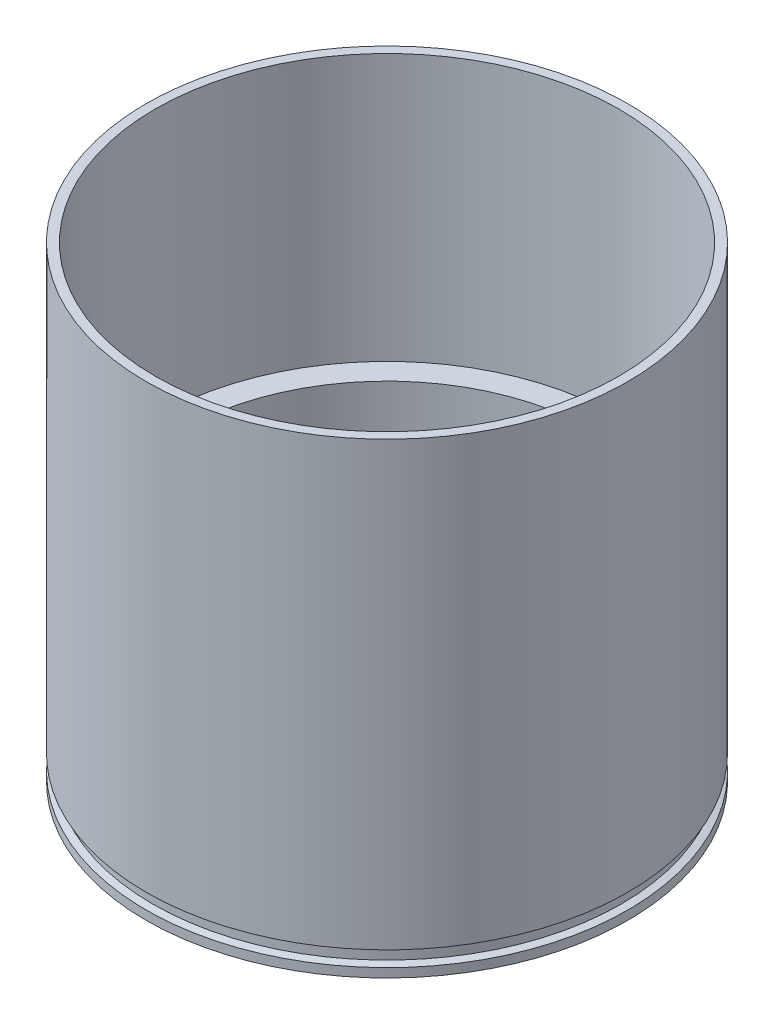
SolidWorks part; units mm, degrees
ref_plane "前基準面" through (0, 0, 0) normal (0, 0, 1) x (1, 0, 0)
ref_plane "上基準面" through (0, 0, 0) normal (0, 1, 0) x (1, 0, 0)
ref_plane "右基準面" through (0, 0, 0) normal (1, 0, 0) x (0, 0, -1)
sketch "草圖1" plane through (0, 0, 0) normal (0, 1, 0) x (1, 0, 0)
  circle A0 centre (0, 0) radius 72.25
  circle A1 centre (0, 0) radius 71
  dimension "D1" = 144.5
  dimension "D2" = 142
extrude "填料-伸長1" add sketch "草圖1" along normal blind 140 contours A1 | A0 A1 region at (-72.0456, 0, 0) region at (0, 0, 0)
sketch "草圖2" plane through (0, 0, 0) normal (0, 0, 1) x (1, 0, 0)
  line L1 (70.25, 6.5) -> (72.25, 6.5)
  line L2 (70.25, 6.5) -> (70.25, 3.5)
  line L3 (70.25, 3.5) -> (72.25, 3.5)
  line L4 (72.25, 6.5) -> (72.25, 3.5)
  line L5 (70.25, 6.5) -> (72.25, 3.5) construction
  line L6 (70.25, 3.5) -> (72.25, 6.5) construction
  line L7 (72.25, 0) -> (72.25, 140) construction
  line L8 (-72.25, 0) -> (72.25, 0) construction
  line L9 (0, 0) -> (0, 52.1316) construction
  point P0 (71.25, 5)
  dimension "D1" = 3
  dimension "D2" = 5
  dimension "D3" = 2
revolve "除料-旋轉1" cut sketch "草圖2" angle 360 about L9
chamfer "導角3" distance 3 angle 15 1 edges at (0, 3.5, -72.25) first distance on face at (0, 3.5, -72.25)
chamfer "導角5" distance 3 angle 15 1 edges at (0, 6.5, -72.25) first distance on face at (0, 6.5, -70.25)
sketch "草圖3" plane through (0, 140, 0) normal (0, 1, 0) x (1, 0, 0)
  circle A0 centre (0, 0) radius 68
  circle A1 centre (0, 0) radius 71
  circle A2 centre (0, 0) radius 72.25
  circle A3 centre (0, 0) radius 72.25 construction
  circle A4 centre (0, 0) radius 62.25
  dimension "D1" = 3
  dimension "D2" = 142
  dimension "D3" = 10
extrude "除料-伸長7" cut sketch "草圖3" against normal blind 135 from surface contours A4 region at (0, 140, 0) starting at face at (0, 140, 72.25)
sketch "草圖7" plane through (0, 5, 0) normal (0, 1, 0) x (1, 0, 0)
  line L1 (-57.2059, 38) -> (-35.2059, 38)
  line L2 (-57.2059, 38) -> (-57.2059, -38)
  line L3 (-57.2059, -38) -> (-35.2059, -38)
  line L4 (-35.2059, 38) -> (-35.2059, -38)
  line L5 (-57.2059, 38) -> (-35.2059, -38) construction
  line L6 (-57.2059, -38) -> (-35.2059, 38) construction
  line L7 (-34, 34) -> (34, 34)
  line L8 (-34, 34) -> (-34, -34)
  line L9 (-34, -34) -> (34, -34)
  line L10 (34, 34) -> (34, -34)
  line L11 (-34, 34) -> (34, -34) construction
  line L12 (-34, -34) -> (34, 34) construction
  point P0 (-46.2059, 0)
  point P5 (16.4653, -3.0749)
  point P6 (-63.1729, -111.779)
  point P7 (0, 0)
  point P8 (-46.2059, 0)
  point P9 (0, 0)
  dimension "D1" = 76
  dimension "D2" = 22
  dimension "D3" = 68
sketch "草圖8" plane through (0, 5, 0) normal (0, 1, 0) x (1, 0, 0)
  circle A0 centre (0, 0) radius 69.5
  dimension "D1" = 139
extrude "除料-伸長9" cut sketch "草圖8" against normal blind 80 from surface starting at face at (0, 140, 62.25)
sketch "草圖9" plane through (0, 0, 0) normal (0, 0, 1) x (1, 0, 0)
  line L0 (72.25, 0) -> (-72.25, 0) construction
  line L1 (-11.4712, 40) -> (8.5288, 40)
  line L2 (-11.4712, 40) -> (-11.4712, 20)
  line L3 (-11.4712, 20) -> (8.5288, 20)
  line L4 (8.5288, 40) -> (8.5288, 20)
  line L5 (-11.4712, 40) -> (8.5288, 20) construction
  line L6 (-11.4712, 20) -> (8.5288, 40) construction
  point P0 (-1.4712, 30)
  point P5 (-1.4712, 21.5735)
  dimension "D1" = 20
  dimension "D2" = 20
  dimension "D3" = 20
